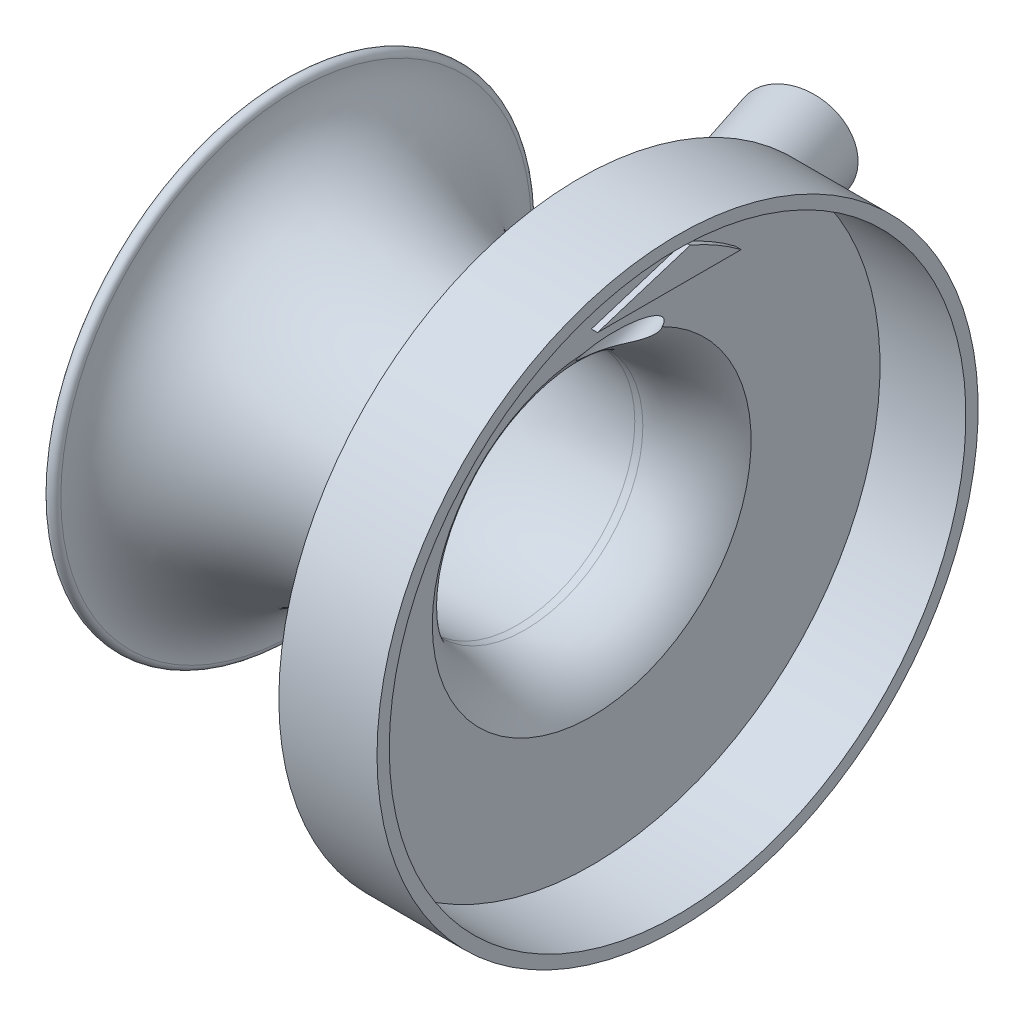
SolidWorks part; units mm, degrees
material "PVC 0.007 Plasticized"
ref_plane "Front Plane" through (0, 0, 0) normal (0, 0, 1) x (1, 0, 0)
ref_plane "Top Plane" through (0, 0, 0) normal (0, 1, 0) x (1, 0, 0)
ref_plane "Right Plane" through (0, 0, 0) normal (1, 0, 0) x (0, 0, -1)
sketch "Sketch1" plane through (0, 0, 0) normal (0, 0, 1) x (1, 0, 0)
  line L0 (-17.78, 33.4033) -> (-17.78, 60.0933)
  line L1 (-34.3222, 33.4033) -> (-9.5791, 33.4033) construction
  line L3 (-34.3222, 0.4033) -> (53.9483, 0.4033) construction
  line L11 (-33.2131, 24.7619) -> (-31.5799, 24.7915)
  line L12 (-17.78, 60.0933) -> (0, 60.0933)
  line L13 (-33.2365, 27.3019) -> (-31.68, 27.3301)
  line L14 (-20.32, 34.0999) -> (-20.32, 62.6333)
  line L15 (-20.32, 62.6333) -> (0, 62.6333)
  line L16 (0, 62.6333) -> (0, 60.0933)
  circle A4 centre (-32.5832, 41.7619) radius 17 construction
  arc A5 (-17.78, 33.4033) -> (-31.5799, 24.7915) centre (-32.5832, 41.7619) cw
  arc A6 (-20.32, 34.0999) -> (-31.68, 27.3301) centre (-32.5832, 41.7619) cw
  arc A7 (-81.5276, 49.1004) -> (-78.9876, 49.1015) centre (-80.2576, 49.101) cw
  ellipse E0 centre (-33.2232, 49.1205) end of major axis (-81.5276, 49.1004) minor radius 24.3586 (-81.5276, 49.1004) -> (-33.2131, 24.7619) ccw
  ellipse E1 centre (-33.2232, 49.1205) end of major axis (-81.5276, 49.1004) minor radius 24.3586 construction
  spline S0 degree 1 poles (-78.9876, 49.1015) (-33.2365, 27.3019) knots 0 0 1 1 construction
  spline S1 degree 3 poles (-78.9876, 49.1015) (-78.9874, 48.4651) (-78.8643, 47.2068) (-78.1154, 44.6473) (-76.1728, 41.3828) (-72.1247, 37.5428) (-66.4667, 34.0595) (-59.4331, 31.146) (-51.3175, 28.9592) (-42.4745, 27.6059) (-36.296, 27.3013) (-33.2365, 27.3019) knots 3.141593 3.141593 3.141593 3.141593 3.239738 3.337883 3.534173 3.730463 3.926753 4.123043 4.319333 4.515623 4.711913 4.711913 4.711913 4.711913
  dimension "D3" = 24.3586
  dimension "D1" = 33.0001
  dimension "D2" = 15.4432
  dimension "D4" = 48.3044
  dimension "D5" = 59.69
  dimension "D10" = 34
  dimension "D11" = 17
  dimension "D12" = 31.5799
  dimension "D9" = 1.27
  dimension "D6" = 17.78
  dimension "D8" = 24.3586
  dimension "D7" = 2.54
  dimension "D13" = 31.68
  dimension "D14" = 34.3222
  dimension "D15" = 0.4033
revolve "Revolve1" add sketch "Sketch1" angle 360 about L3
ref_axis "Axis1" through (0, 65.659, 0) along (0, -1, 0)
ref_plane "Plane1" through (0, 0, 0) normal (-0.309, 0, -0.9511) x (0, -1, 0)
ref_plane "Plane2" through (-13.3434, 0, -41.0666) normal (-0.309, 0, -0.9511) x (0, -1, 0)
sketch "Sketch2" plane through (-13.3434, 0, -41.0666) normal (-0.309, 0, -0.9511) x (0, -1, 0)
  line L0 (-33.0001, 18.6255) -> (-26.9006, 18.6255) construction
  circle A0 centre (-30.8893, 15.4505) radius 3.175
  circle A1 centre (-30.8893, 15.4505) radius 10.16
  circle A2 centre (-30.8893, 15.4505) radius 5.5562
  ellipse E0 centre (0, 18.6255) end of major axis (-33.0001, 18.6255) minor radius 9.0224 construction
  dimension "D1" = 6.35
  dimension "D2" = 20.32
  dimension "D3" = 11.1125
  dimension "D4" = 0
extrude "Boss-Extrude1" add sketch "Sketch2" against normal up to next separate body contours A2 A0 region at (-28.0376, 36.2884, -36.2922)
extrude "Cut-Extrude1" cut sketch "Sketch2<3>" along direction (-0.309, 0, -0.9511) on the side against the normal blind 40.64 and the other way through all contours A0 region at (-28.0376, 30.8893, -36.2922)
sketch "Sketch2<3>" plane through (-13.3434, 0, -41.0666) normal (-0.309, 0, -0.9511) x (0, -1, 0) same geometry as "Sketch2"
extrude "Boss-Extrude3" add sketch "Sketch2<4>" against normal blind 1.016 and the other way blind 25.4 contours A1 A2 region at (-28.0376, 40.7619, -36.2922)
sketch "Sketch2<4>" plane through (-13.3434, 0, -41.0666) normal (-0.309, 0, -0.9511) x (0, -1, 0) same geometry as "Sketch2"
sketch "Sketch4" plane through (-17.78, 0, 0) normal (1, 0, 0) x (0, 0, -1)
  line L0 (-0.0695, 36.9094) -> (29.6804, 36.9094) construction
  line L1 (-0.0695, 36.9094) -> (19.1351, 42.9646)
  line L2 (-0.0695, 36.9094) -> (29.6804, 36.9094)
  arc A0 (19.1351, 42.9646) -> (29.6804, 36.9094) centre (-0.0695, -2.6907) cw
  circle A1 centre (-0.0695, -2.6907) radius 39.6001 construction
  point P5 (-2.5111, -43.1518)
  dimension "D1" = 79.2001
  dimension "D2" = 17.5
extrude "Boss-Extrude4" add sketch "Sketch4" along normal blind 1.27
